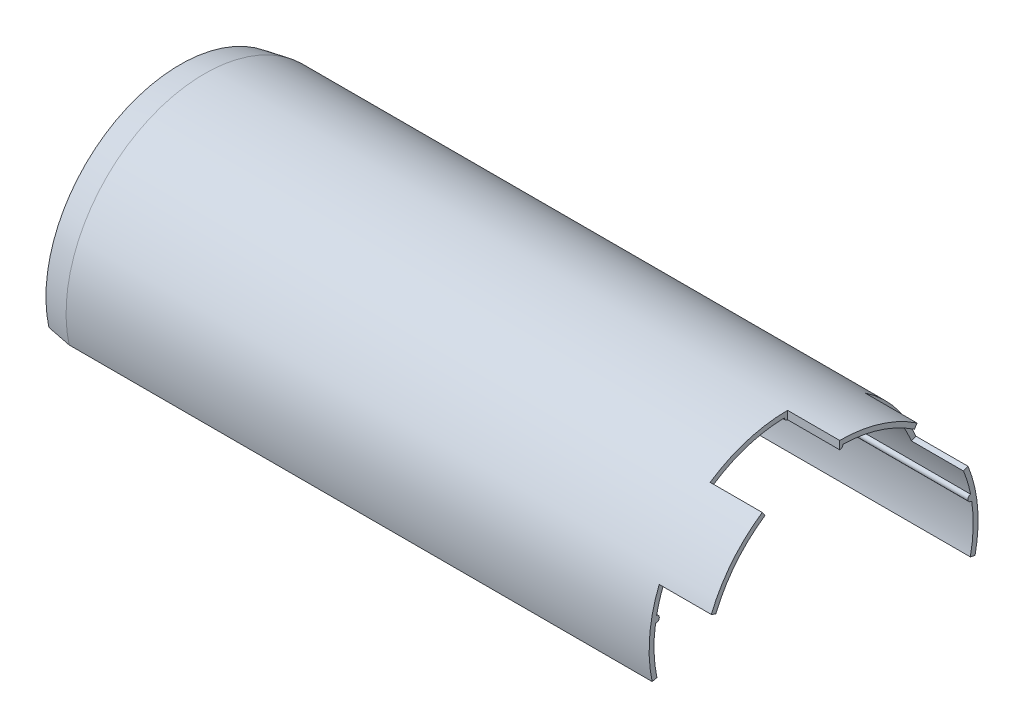
SolidWorks part; units mm, degrees
note: '?' marks a value the reader was unsure of.
material "PETG"
ref_plane "Front Plane" through (0, 0, 0) normal (0, 0, 1) x (1, 0, 0)
ref_plane "Top Plane" through (0, 0, 0) normal (0, 1, 0) x (1, 0, 0)
ref_plane "Right Plane" through (0, 0, 0) normal (1, 0, 0) x (0, 0, -1)
curve "Curve1"
  spline degree 3 poles (0, 0, 0) (-0.0123, 3.8916, 0) (-0.0274, 8.685, 0) (0.3616, 14.0857, 0) (0.5761, 16.0905, 0) (0.7825, 17.6048, 0) (0.9862, 18.8543, 0) (1.1887, 19.9315, 0) (1.3904, 20.8857, 0) (1.5917, 21.7465, 0) (1.7927, 22.5337, 0) (1.9935, 23.2611, 0) (2.1942, 23.9386, 0) (2.3947, 24.5739, 0) (2.5952, 25.1728, 0) (2.7956, 25.7401, 0) (2.9959, 26.2796, 0) (3.1962, 26.7943, 0) (3.3965, 27.2868, 0) (3.5967, 27.7594, 0) (3.7969, 28.2139, 0) (3.9971, 28.6519, 0) (4.1973, 29.0748, 0) (4.3974, 29.4838, 0) (4.5976, 29.8799, 0) (4.7977, 30.2641, 0) (4.9978, 30.6373, 0) (5.1979, 31.0001, 0) (5.398, 31.3533, 0) (5.5981, 31.6974, 0) (5.7982, 32.033, 0) (5.9983, 32.3606, 0) (6.1984, 32.6807, 0) (6.3985, 32.9935, 0) (6.5985, 33.2996, 0) (6.7986, 33.5993, 0) (6.9986, 33.8929, 0) (7.1987, 34.1806, 0) (7.3987, 34.4628, 0) (7.5988, 34.7397, 0) (7.7988, 35.0115, 0) (7.9989, 35.2785, 0) (8.1989, 35.5408, 0) (8.399, 35.7988, 0) (8.599, 36.0524, 0) (8.799, 36.3019, 0) (8.9991, 36.5476, 0) (9.1991, 36.7894, 0) (9.3991, 37.0275, 0) (9.5992, 37.2622, 0) (9.7992, 37.4934, 0) (9.9992, 37.7214, 0) (10.1992, 37.9461, 0) (10.3993, 38.1679, 0) (10.5993, 38.3866, 0) (10.7993, 38.6025, 0) (10.9993, 38.8156, 0) (11.1993, 39.026, 0) (11.3994, 39.2338, 0) (11.5994, 39.4391, 0) (11.7994, 39.6419, 0) (11.9994, 39.8422, 0) (12.1994, 40.0403, 0) (12.3995, 40.2361, 0) (12.5995, 40.4297, 0) (12.7995, 40.6212, 0) (12.9995, 40.8106, 0) (13.1995, 40.998, 0) (13.3995, 41.1834, 0) (13.5995, 41.3668, 0) (13.7995, 41.5484, 0) (13.9996, 41.7281, 0) (14.1996, 41.9061, 0) (14.3996, 42.0823, 0) (14.5996, 42.2568, 0) (14.7996, 42.4296, 0) (14.9996, 42.6008, 0) (15.1996, 42.7705, 0) (15.3996, 42.9385, 0) (15.5996, 43.1051, 0) (15.7996, 43.2701, 0) (15.9997, 43.4337, 0) (16.1997, 43.5959, 0) (16.3997, 43.7567, 0) (16.5997, 43.9161, 0) (16.7997, 44.0742, 0) (16.9997, 44.2309, 0) (17.1997, 44.3864, 0) (17.3997, 44.5406, 0) (17.5997, 44.6936, 0) (17.7997, 44.8453, 0) (17.9997, 44.9959, 0) (18.1997, 45.1453, 0) (18.3997, 45.2936, 0) (18.5997, 45.4407, 0) (18.7997, 45.5868, 0) (18.9997, 45.7317, 0) (19.1998, 45.8756, 0) (19.3998, 46.0185, 0) (19.5998, 46.1603, 0) (19.7998, 46.3011, 0) (19.9998, 46.4409, 0) (20.1998, 46.5797, 0) (20.3998, 46.7176, 0) (20.5998, 46.8546, 0) (20.7998, 46.9906, 0) (20.9998, 47.1257, 0) (21.1998, 47.2599, 0) (21.3998, 47.3932, 0) (21.5998, 47.5256, 0) (21.7998, 47.6572, 0) (21.9998, 47.788, 0) (22.1998, 47.9179, 0) (22.3998, 48.047, 0) (22.5998, 48.1753, 0) (22.7998, 48.3028, 0) (22.9998, 48.4295, 0) (23.1998, 48.5555, 0) (23.3998, 48.6807, 0) (23.5998, 48.8051, 0) (23.7998, 48.9288, 0) (23.9998, 49.0518, 0) (24.1998, 49.1741, 0) (24.3998, 49.2957, 0) (24.5998, 49.4165, 0) (24.7999, 49.5367, 0) (24.9999, 49.6562, 0) (25.1999, 49.7751, 0) (25.3999, 49.8933, 0) (25.5999, 50.0108, 0) (25.7999, 50.1277, 0) (25.9999, 50.2439, 0) (26.1999, 50.3596, 0) (26.3999, 50.4746, 0) (26.5999, 50.589, 0) (26.7999, 50.7028, 0) (26.9999, 50.8161, 0) (27.1999, 50.9287, 0) (27.3999, 51.0407, 0) (27.5999, 51.1522, 0) (27.7999, 51.2631, 0) (27.9999, 51.3735, 0) (28.1999, 51.4833, 0) (28.3999, 51.5926, 0) (28.5999, 51.7013, 0) (28.7999, 51.8095, 0) (28.9999, 51.9172, 0) (29.1999, 52.0243, 0) (29.3999, 52.131, 0) (29.5999, 52.2371, 0) (29.7999, 52.3428, 0) (29.9999, 52.4479, 0) (30.1999, 52.5526, 0) (30.3999, 52.6567, 0) (30.5999, 52.7604, 0) (30.7999, 52.8636, 0) (30.9999, 52.9664, 0) (31.1999, 53.0687, 0) (31.3999, 53.1705, 0) (31.5999, 53.2719, 0) (31.7999, 53.3728, 0) (31.9999, 53.4733, 0) (32.1999, 53.5733, 0) (32.3999, 53.6729, 0) (32.5999, 53.7721, 0) (32.7999, 53.8709, 0) (32.9999, 53.9692, 0) (33.1999, 54.0671, 0) (33.3999, 54.1646, 0) (33.5999, 54.2617, 0) (33.7999, 54.3584, 0) (33.9999, 54.4547, 0) (34.1999, 54.5506, 0) (34.3999, 54.6461, 0) (34.5999, 54.7412, 0) (34.7999, 54.836, 0) (34.9999, 54.9303, 0) (35.1999, 55.0243, 0) (35.3999, 55.1179, 0) (35.5999, 55.2111, 0) (35.7999, 55.304, 0) (35.9999, 55.3965, 0) (36.1999, 55.4887, 0) (36.3999, 55.5805, 0) (36.5999, 55.6719, 0) (36.7999, 55.763, 0) (36.9999, 55.8537, 0) (37.1999, 55.9441, 0) (37.3999, 56.0342, 0) (37.5999, 56.1239, 0) (37.7999, 56.2133, 0) (37.9999, 56.3024, 0) (38.1999, 56.3911, 0) (38.3999, 56.4795, 0) (38.5999, 56.5676, 0) (38.7999, 56.6554, 0) (38.9999, 56.7428, 0) (39.1999, 56.83, 0) (39.3999, 56.9168, 0) (39.5999, 57.0033, 0) (39.7999, 57.0896, 0) (39.9999, 57.1755, 0) (40.1999, 57.2611, 0) (40.3999, 57.3464, 0) (40.5999, 57.4314, 0) (40.7999, 57.5161, 0) (40.9999, 57.6006, 0) (41.1999, 57.6847, 0) (41.3999, 57.7686, 0) (41.6, 57.8522, 0) (41.8, 57.9355, 0) (42, 58.0185, 0) (42.2, 58.1012, 0) (42.4, 58.1837, 0) (42.6, 58.2659, 0) (42.8, 58.3479, 0) (43, 58.4295, 0) (43.2, 58.5109, 0) (43.4, 58.592, 0) (43.6, 58.6729, 0) (43.8, 58.7535, 0) (44, 58.8339, 0) (44.2, 58.914, 0) (44.4, 58.9938, 0) (44.6, 59.0734, 0) (44.8, 59.1528, 0) (45, 59.2319, 0) (45.2, 59.3107, 0) (45.4, 59.3893, 0) (45.6, 59.4677, 0) (45.8, 59.5458, 0) (46, 59.6237, 0) (46.2, 59.7014, 0) (46.4, 59.7788, 0) (46.6, 59.856, 0) (46.8, 59.9329, 0) (47, 60.0096, 0) (47.2, 60.0861, 0) (47.4, 60.1624, 0) (47.6, 60.2385, 0) (47.8, 60.3143, 0) (48, 60.3899, 0) (48.2, 60.4652, 0) (48.4, 60.5404, 0) (48.6, 60.6153, 0) (48.8, 60.6901, 0) (49, 60.7646, 0) (49.2, 60.8389, 0) (49.4, 60.913, 0) (49.6, 60.9869, 0) (49.8, 61.0605, 0) (50, 61.134, 0) (50.2, 61.2072, 0) (50.4, 61.2803, 0) (50.6, 61.3531, 0) (50.8, 61.4258, 0) (51, 61.4982, 0) (51.2, 61.5705, 0) (51.4, 61.6426, 0) (51.6, 61.7144, 0) (51.8, 61.7861, 0) (52, 61.8575, 0) (52.2, 61.9288, 0) (52.4, 61.9999, 0) (52.6, 62.0708, 0) (52.8, 62.1415, 0) (53, 62.212, 0) (53.2, 62.2824, 0) (53.4, 62.3525, 0) (53.6, 62.4225, 0) (53.8, 62.4923, 0) (54, 62.5619, 0) (54.2, 62.6313, 0) (54.4, 62.7006, 0) (54.6, 62.7696, 0) (54.8, 62.8385, 0) (55, 62.9072, 0) (55.2, 62.9758, 0) (55.4, 63.0441, 0) (55.6, 63.1123, 0) (55.8, 63.1803, 0) (56, 63.2482, 0) (56.2, 63.3159, 0) (56.4, 63.3834, 0) (56.6, 63.4507, 0) (56.8, 63.5179, 0) (57, 63.5849, 0) (57.2, 63.6518, 0) (57.4, 63.7185, 0) (57.6, 63.785, 0) (57.8, 63.8513, 0) (58, 63.9175, 0) (58.2, 63.9836, 0) (58.4, 64.0495, 0) (58.6, 64.1152, 0) (58.8, 64.1808, 0) (59, 64.2462, 0) (59.2, 64.3114, 0) (59.4, 64.3765, 0) (59.6, 64.4415, 0) (59.8, 64.5063, 0) (60, 64.5709, 0) (60.2, 64.6354, 0) (60.4, 64.6998, 0) (60.6, 64.764, 0) (60.8, 64.828, 0) (61, 64.8919, 0) (61.2, 64.9557, 0) (61.4, 65.0193, 0) (61.6, 65.0827, 0) (61.8, 65.1461, 0) (62, 65.2092, 0) (62.2, 65.2723, 0) (62.4, 65.3352, 0) (62.6, 65.3979, 0) (62.8, 65.4605, 0) (63, 65.523, 0) (63.2, 65.5853, 0) (63.4, 65.6475, 0) (63.6, 65.7096, 0) (63.8, 65.7715, 0) (64, 65.8333, 0) (64.2, 65.895, 0) (64.4, 65.9565, 0) (64.6, 66.0179, 0) (64.8, 66.0791, 0) (65, 66.1402, 0) (65.2, 66.2012, 0) (65.4, 66.2621, 0) (65.6, 66.3228, 0) (65.8, 66.3834, 0) (66, 66.4439, 0) (66.2, 66.5042, 0) (66.4, 66.5644, 0) (66.6, 66.6245, 0) (66.8, 66.6845, 0) (67, 66.7443, 0) (67.2, 66.804, 0) (67.4, 66.8636, 0) (67.6, 66.923, 0) (67.8, 66.9824, 0) (68, 67.0416, 0) (68.2, 67.1007, 0) (68.4, 67.1597, 0) (68.6, 67.2185, 0) (68.8, 67.2772, 0) (69, 67.3359, 0) (69.2, 67.3943, 0) (69.4, 67.4527, 0) (69.6, 67.511, 0) (69.8, 67.5691, 0) (70, 67.6271, 0) (70.2, 67.6851, 0) (70.4, 67.7428, 0) (70.6, 67.8005, 0) (70.8, 67.8581, 0) (71, 67.9155, 0) (71.2, 67.9729, 0) (71.4, 68.0301, 0) (71.6, 68.0872, 0) (71.8, 68.1442, 0) (72, 68.2011, 0) (72.2, 68.2579, 0) (72.4, 68.3145, 0) (72.6, 68.3711, 0) (72.8, 68.4276, 0) (73, 68.4839, 0) (73.2, 68.5401, 0) (73.4, 68.5963, 0) (73.6, 68.6523, 0) (73.8, 68.7082, 0) (74, 68.764, 0) (74.2, 68.8197, 0) (74.4, 68.8753, 0) (74.6, 68.9308, 0) (74.8, 68.9862, 0) (75, 69.0415, 0) (75.2, 69.0966, 0) (75.4, 69.1517, 0) (75.6, 69.2067, 0) (75.8, 69.2616, 0) (76, 69.3164, 0) (76.2, 69.371, 0) (76.4, 69.4256, 0) (76.6, 69.4801, 0) (76.8, 69.5344, 0) (77, 69.5887, 0) (77.2, 69.6429, 0) (77.4, 69.697, 0) (77.6, 69.751, 0) (77.8, 69.8048, 0) (78, 69.8586, 0) (78.2, 69.9123, 0) (78.4, 69.9659, 0) (78.6, 70.0194, 0) (78.8, 70.0728, 0) (79, 70.1261, 0) (79.2, 70.1793, 0) (79.4, 70.2324, 0) (79.6, 70.2855, 0) (79.8, 70.3384, 0) (80, 70.3912, 0) (80.2, 70.444, 0) (80.4, 70.4966, 0) (80.6, 70.5492, 0) (80.8, 70.6017, 0) (81, 70.6541, 0) (81.2, 70.7064, 0) (81.4, 70.7586, 0) (81.6, 70.8107, 0) (81.8, 70.8627, 0) (82, 70.9146, 0) (82.2, 70.9665, 0) (82.4, 71.0182, 0) (82.6, 71.0699, 0) (82.8, 71.1215, 0) (83, 71.173, 0) (83.2, 71.2244, 0) (83.4, 71.2757, 0) (83.6, 71.3269, 0) (83.8, 71.3781, 0) (84, 71.4291, 0) (84.2, 71.4801, 0) (84.4, 71.531, 0) (84.6, 71.5818, 0) (84.8, 71.6325, 0) (85, 71.6832, 0) (85.2, 71.7337, 0) (85.4, 71.7842, 0) (85.6, 71.8346, 0) (85.8, 71.8849, 0) (86, 71.9351, 0) (86.2, 71.9853, 0) (86.4, 72.0354, 0) (86.6, 72.0853, 0) (86.8, 72.1352, 0) (87, 72.1851, 0) (87.2, 72.2348, 0) (87.4, 72.2845, 0) (87.6, 72.3341, 0) (87.8, 72.3836, 0) (88, 72.433, 0) (88.2, 72.4823, 0) (88.4, 72.5316, 0) (88.6, 72.5808, 0) (88.8, 72.6299, 0) (89, 72.6789, 0) (89.2, 72.7279, 0) (89.4, 72.7768, 0) (89.6, 72.8256, 0) (89.8, 72.8743, 0) (90, 72.923, 0) (90.2, 72.9716, 0) (90.4, 73.0201, 0) (90.6, 73.0685, 0) (90.8, 73.1168, 0) (91, 73.1651, 0) (91.2, 73.2133, 0) (91.4, 73.2614, 0) (91.6, 73.3095, 0) (91.8, 73.3575, 0) (92, 73.4054, 0) (92.2, 73.4532, 0) (92.4, 73.501, 0) (92.6, 73.5487, 0) (92.8, 73.5963, 0) (93, 73.6439, 0) (93.2, 73.6913, 0) (93.4, 73.7387, 0) (93.6, 73.7861, 0) (93.8, 73.8333, 0) (94, 73.8805, 0) (94.2, 73.9276, 0) (94.4, 73.9747, 0) (94.6, 74.0217, 0) (94.8, 74.0686, 0) (95, 74.1154, 0) (95.2, 74.1622, 0) (95.4, 74.2089, 0) (95.6, 74.2556, 0) (95.8, 74.3021, 0) (96, 74.3486, 0) (96.2, 74.3951, 0) (96.4, 74.4414, 0) (96.6, 74.4877, 0) (96.8, 74.534, 0) (97, 74.5801, 0) (97.2, 74.6262, 0) (97.4, 74.6723, 0) (97.6, 74.7182, 0) (97.8, 74.7641, 0) (98, 74.81, 0) (98.2, 74.8557, 0) (98.4, 74.9014, 0) (98.6, 74.9471, 0) (98.8, 74.9926, 0) (99, 75.0382, 0) (99.2, 75.0836, 0) (99.4, 75.129, 0) (99.6, 75.1743, 0) (99.8, 75.2196, 0) (100, 75.2647, 0) (100.2, 75.3099, 0) (100.4, 75.3549, 0) (100.6, 75.3999, 0) (100.8, 75.4449, 0) (101, 75.4898, 0) (101.2, 75.5346, 0) (101.4, 75.5793, 0) (101.6, 75.624, 0) (101.8, 75.6686, 0) (102, 75.7132, 0) (102.2, 75.7577, 0) (102.4, 75.8022, 0) (102.6, 75.8465, 0) (102.8, 75.8909, 0) (103, 75.9351, 0) (103.2, 75.9793, 0) (103.4, 76.0235, 0) (103.6, 76.0676, 0) (103.8, 76.1116, 0) (104, 76.1556, 0) (104.2, 76.1995, 0) (104.4, 76.2433, 0) (104.6, 76.2871, 0) (104.8, 76.3308, 0) (105, 76.3745, 0) (105.2, 76.4181, 0) (105.4, 76.4617, 0) (105.6, 76.5052, 0) (105.8, 76.5486, 0) (106, 76.592, 0) (106.2, 76.6353, 0) (106.4, 76.6786, 0) (106.6, 76.7218, 0) (106.8, 76.7649, 0) (107, 76.808, 0) (107.2, 76.8511, 0) (107.4, 76.8941, 0) (107.6, 76.937, 0) (107.8, 76.9799, 0) (108, 77.0227, 0) (108.2, 77.0655, 0) (108.4, 77.1082, 0) (108.6, 77.1508, 0) (108.8, 77.1934, 0) (109, 77.236, 0) (109.2, 77.2784, 0) (109.4, 77.3209, 0) (109.6, 77.3633, 0) (109.8, 77.4056, 0) (110, 77.4479, 0) (110.2, 77.4901, 0) (110.4, 77.5322, 0) (110.6, 77.5743, 0) (110.8, 77.6164, 0) (111, 77.6584, 0) (111.2, 77.7004, 0) (111.4, 77.7423, 0) (111.6, 77.7841, 0) (111.8, 77.8259, 0) (112, 77.8676, 0) (112.2, 77.9093, 0) (112.4, 77.951, 0) (112.6, 77.9925, 0) (112.8, 78.0341, 0) (113, 78.0756, 0) (113.2, 78.117, 0) (113.4, 78.1584, 0) (113.6, 78.1997, 0) (113.8, 78.241, 0) (114, 78.2822, 0) (114.2, 78.3234, 0) (114.4, 78.3645, 0) (114.6, 78.4056, 0) (114.8, 78.4466, 0) (115, 78.4876, 0) (115.2, 78.5285, 0) (115.4, 78.5694, 0) (115.6, 78.6102, 0) (115.8, 78.651, 0) (116, 78.6917, 0) (116.2, 78.7324, 0) (116.4, 78.773, 0) (116.6, 78.8136, 0) (116.8, 78.8541, 0) (117, 78.8946, 0) (117.2, 78.935, 0) (117.4, 78.9754, 0) (117.6, 79.0158, 0) (117.8, 79.0561, 0) (118, 79.0963, 0) (118.2, 79.1365, 0) (118.4, 79.1766, 0) (118.6, 79.2167, 0) (118.8, 79.2568, 0) (119, 79.2968, 0) (119.2, 79.3368, 0) (119.4, 79.3767, 0) (119.6, 79.4165, 0) (119.8, 79.4564, 0) (120, 79.4961, 0) (120.2, 79.5358, 0) (120.4, 79.5755, 0) (120.6, 79.6152, 0) (120.8, 79.6547, 0) (121, 79.6943, 0) (121.2, 79.7338, 0) (121.4, 79.7732, 0) (121.6, 79.8126, 0) (121.8, 79.852, 0) (122, 79.8913, 0) (122.2, 79.9306, 0) (122.4, 79.9698, 0) (122.6, 80.009, 0) (122.8, 80.0481, 0) (123, 80.0872, 0) (123.2, 80.1262, 0) (123.4, 80.1652, 0) (123.6, 80.2042, 0) (123.8, 80.2431, 0) (124, 80.282, 0) (124.2, 80.3208, 0) (124.4, 80.3596, 0) (124.6, 80.3983, 0) (124.8, 80.437, 0) (125, 80.4757, 0) (125.2, 80.5143, 0) (125.4, 80.5528, 0) (125.6, 80.5914, 0) (125.8, 80.6298, 0) (126, 80.6683, 0) (126.2, 80.7067, 0) (126.4, 80.745, 0) (126.6, 80.7833, 0) (126.8, 80.8216, 0) (127, 80.8598, 0) (127.2, 80.898, 0) (127.4, 80.9361, 0) (127.6, 80.9742, 0) (127.8, 81.0123, 0) (128, 81.0503, 0) (128.2, 81.0883, 0) (128.4, 81.1262, 0) (128.6, 81.1641, 0) (128.8, 81.2019, 0) (129, 81.2397, 0) (129.2, 81.2775, 0) (129.4, 81.3152, 0) (129.6, 81.3529, 0) (129.8, 81.3906, 0) (130, 81.4282, 0) (130.2, 81.4657, 0) (130.4, 81.5032, 0) (130.6, 81.5407, 0) (130.8, 81.5782, 0) (131, 81.6156, 0) (131.2, 81.6529, 0) (131.4, 81.6902, 0) (131.6, 81.7275, 0) (131.8, 81.7648, 0) (132, 81.802, 0) (132.2, 81.8391, 0) (132.4, 81.8763, 0) (132.6, 81.9133, 0) (132.8, 81.9504, 0) (133, 81.9874, 0) (133.2, 82.0244, 0) (133.4, 82.0613, 0) (133.6, 82.0982, 0) (133.8, 82.135, 0) (134, 82.1718, 0) (134.2, 82.2086, 0) (134.4, 82.2454, 0) (134.6, 82.282, 0) (134.8, 82.3187, 0) (135, 82.3553, 0) (135.2, 82.3919, 0) (135.4, 82.4285, 0) (135.6, 82.465, 0) (135.8, 82.5014, 0) (136, 82.5379, 0) (136.2, 82.5743, 0) (136.4, 82.6106, 0) (136.6, 82.6469, 0) (136.8, 82.6832, 0) (137, 82.7195, 0) (137.2, 82.7557, 0) (137.4, 82.7919, 0) (137.6, 82.828, 0) (137.8, 82.8641, 0) (138, 82.9001, 0) (138.2, 82.9362, 0) (138.4, 82.9722, 0) (138.6, 83.0081, 0) (138.8, 83.044, 0) (139, 83.0799, 0) (139.2, 83.1158, 0) (139.4, 83.1516, 0) (139.6, 83.1873, 0) (139.8, 83.2231, 0) (140, 83.2588, 0) (140.2, 83.2944, 0) (140.4, 83.3301, 0) (140.6, 83.3657, 0) (140.8, 83.4012, 0) (141, 83.4367, 0) (141.2, 83.4722, 0) (141.4, 83.5077, 0) (141.6, 83.5431, 0) (141.8, 83.5785, 0) (142, 83.6138, 0) (142.2, 83.6491, 0) (142.4, 83.6844, 0) (142.6, 83.7197, 0) (142.8, 83.7549, 0) (143, 83.79, 0) (143.2, 83.8252, 0) (143.4, 83.8603, 0) (143.6, 83.8954, 0) (143.8, 83.9304, 0) (144, 83.9654, 0) (144.2, 84.0004, 0) (144.4, 84.0353, 0) (144.6, 84.0702, 0) (144.8, 84.1051, 0) (145, 84.1399, 0) (145.2, 84.1747, 0) (145.4, 84.2095, 0) (145.6, 84.2442, 0) (145.8, 84.2789, 0) (146, 84.3136, 0) (146.2, 84.3482, 0) (146.4, 84.3828, 0) (146.6, 84.4174, 0) (146.8, 84.4519, 0) (147, 84.4864, 0) (147.2, 84.5209, 0) (147.4, 84.5553, 0) (147.6, 84.5897, 0) (147.8, 84.6241, 0) (148, 84.6584, 0) (148.2, 84.6927, 0) (148.4, 84.727, 0) (148.6, 84.7612, 0) (148.8, 84.7954, 0) (149, 84.8296, 0) (149.2, 84.8638, 0) (149.4, 84.8979, 0) (149.6, 84.9319, 0) (149.8, 84.966, 0) (149.9333, 84.9887, 0) (150, 85, 0) knots 0 0 0 0 0.061462 0.075706 0.085548 0.093322 0.099856 0.105554 0.110643 0.115268 0.119525 0.123482 0.127192 0.130691 0.13401 0.137173 0.140199 0.143104 0.145901 0.148602 0.151215 0.15375 0.156213 0.158609 0.160946 0.163227 0.165456 0.167638 0.169775 0.171871 0.173928 0.17595 0.177937 0.179893 0.181819 0.183716 0.185587 0.187433 0.189255 0.191054 0.192831 0.194589 0.196326 0.198045 0.199747 0.201431 0.2031 0.204753 0.206391 0.208015 0.209626 0.211223 0.212808 0.214381 0.215942 0.217493 0.219032 0.220561 0.22208 0.22359 0.225091 0.226582 0.228065 0.229539 0.231006 0.232464 0.233915 0.235359 0.236795 0.238225 0.239648 0.241065 0.242475 0.243879 0.245277 0.24667 0.248057 0.249438 0.250814 0.252185 0.253551 0.254913 0.256269 0.257621 0.258968 0.260311 0.26165 0.262984 0.264315 0.265641 0.266964 0.268282 0.269598 0.270909 0.272217 0.273522 0.274823 0.276121 0.277416 0.278707 0.279996 0.281281 0.282564 0.283843 0.28512 0.286394 0.287666 0.288935 0.290201 0.291465 0.292726 0.293985 0.295241 0.296495 0.297747 0.298996 0.300243 0.301489 0.302732 0.303972 0.305211 0.306448 0.307683 0.308916 0.310147 0.311376 0.312604 0.313829 0.315053 0.316275 0.317495 0.318714 0.319931 0.321147 0.32236 0.323573 0.324783 0.325993 0.3272 0.328406 0.329611 0.330815 0.332017 0.333217 0.334416 0.335614 0.336811 0.338006 0.3392 0.340393 0.341584 0.342775 0.343964 0.345152 0.346339 0.347524 0.348709 0.349892 0.351074 0.352256 0.353436 0.354615 0.355793 0.35697 0.358146 0.359321 0.360495 0.361668 0.36284 0.364011 0.365182 0.366351 0.36752 0.368687 0.369854 0.37102 0.372185 0.373349 0.374512 0.375674 0.376836 0.377997 0.379157 0.380316 0.381475 0.382632 0.383789 0.384946 0.386101 0.387256 0.38841 0.389563 0.390716 0.391868 0.393019 0.39417 0.39532 0.396469 0.397618 0.398766 0.399913 0.40106 0.402206 0.403351 0.404496 0.40564 0.406784 0.407927 0.409069 0.410211 0.411353 0.412493 0.413633 0.414773 0.415912 0.417051 0.418189 0.419326 0.420463 0.4216 0.422736 0.423871 0.425006 0.426141 0.427275 0.428408 0.429541 0.430674 0.431806 0.432937 0.434068 0.435199 0.436329 0.437459 0.438588 0.439717 0.440846 0.441974 0.443101 0.444229 0.445355 0.446482 0.447608 0.448733 0.449858 0.450983 0.452107 0.453231 0.454355 0.455478 0.456601 0.457723 0.458845 0.459967 0.461088 0.462209 0.46333 0.46445 0.46557 0.46669 0.467809 0.468928 0.470046 0.471164 0.472282 0.4734 0.474517 0.475634 0.47675 0.477866 0.478982 0.480098 0.481213 0.482328 0.483443 0.484557 0.485671 0.486785 0.487898 0.489011 0.490124 0.491237 0.492349 0.493461 0.494573 0.495684 0.496796 0.497906 0.499017 0.500127 0.501237 0.502347 0.503457 0.504566 0.505675 0.506784 0.507892 0.509001 0.510109 0.511216 0.512324 0.513431 0.514538 0.515645 0.516752 0.517858 0.518964 0.52007 0.521175 0.522281 0.523386 0.524491 0.525595 0.5267 0.527804 0.528908 0.530012 0.531116 0.532219 0.533322 0.534425 0.535528 0.53663 0.537733 0.538835 0.539937 0.541038 0.54214 0.543241 0.544342 0.545443 0.546544 0.547644 0.548745 0.549845 0.550945 0.552044 0.553144 0.554243 0.555342 0.556441 0.55754 0.558639 0.559737 0.560836 0.561934 0.563032 0.564129 0.565227 0.566324 0.567421 0.568518 0.569615 0.570712 0.571809 0.572905 0.574001 0.575097 0.576193 0.577289 0.578384 0.57948 0.580575 0.58167 0.582765 0.58386 0.584954 0.586049 0.587143 0.588237 0.589331 0.590425 0.591519 0.592612 0.593706 0.594799 0.595892 0.596985 0.598078 0.59917 0.600263 0.601355 0.602448 0.60354 0.604632 0.605724 0.606815 0.607907 0.608998 0.61009 0.611181 0.612272 0.613363 0.614453 0.615544 0.616635 0.617725 0.618815 0.619905 0.620995 0.622085 0.623175 0.624265 0.625354 0.626443 0.627533 0.628622 0.629711 0.6308 0.631888 0.632977 0.634066 0.635154 0.636242 0.637331 0.638419 0.639507 0.640594 0.641682 0.64277 0.643857 0.644945 0.646032 0.647119 0.648206 0.649293 0.65038 0.651467 0.652553 0.65364 0.654726 0.655813 0.656899 0.657985 0.659071 0.660157 0.661243 0.662328 0.663414 0.664499 0.665585 0.66667 0.667755 0.66884 0.669925 0.67101 0.672095 0.67318 0.674264 0.675349 0.676433 0.677518 0.678602 0.679686 0.68077 0.681854 0.682938 0.684022 0.685105 0.686189 0.687272 0.688356 0.689439 0.690522 0.691605 0.692688 0.693771 0.694854 0.695937 0.69702 0.698102 0.699185 0.700267 0.70135 0.702432 0.703514 0.704596 0.705678 0.70676 0.707842 0.708924 0.710006 0.711087 0.712169 0.71325 0.714332 0.715413 0.716494 0.717575 0.718656 0.719737 0.720818 0.721899 0.72298 0.724061 0.725141 0.726222 0.727302 0.728382 0.729463 0.730543 0.731623 0.732703 0.733783 0.734863 0.735943 0.737023 0.738103 0.739182 0.740262 0.741341 0.742421 0.7435 0.744579 0.745659 0.746738 0.747817 0.748896 0.749975 0.751054 0.752133 0.753211 0.75429 0.755369 0.756447 0.757526 0.758604 0.759682 0.760761 0.761839 0.762917 0.763995 0.765073 0.766151 0.767229 0.768307 0.769385 0.770462 0.77154 0.772618 0.773695 0.774773 0.77585 0.776927 0.778005 0.779082 0.780159 0.781236 0.782313 0.78339 0.784467 0.785544 0.786621 0.787698 0.788774 0.789851 0.790928 0.792004 0.793081 0.794157 0.795233 0.79631 0.797386 0.798462 0.799538 0.800614 0.80169 0.802766 0.803842 0.804918 0.805994 0.80707 0.808145 0.809221 0.810296 0.811372 0.812447 0.813523 0.814598 0.815674 0.816749 0.817824 0.818899 0.819974 0.821049 0.822124 0.823199 0.824274 0.825349 0.826424 0.827499 0.828573 0.829648 0.830723 0.831797 0.832872 0.833946 0.835021 0.836095 0.837169 0.838244 0.839318 0.840392 0.841466 0.84254 0.843614 0.844688 0.845762 0.846836 0.84791 0.848984 0.850058 0.851131 0.852205 0.853279 0.854352 0.855426 0.856499 0.857573 0.858646 0.859719 0.860793 0.861866 0.862939 0.864012 0.865085 0.866159 0.867232 0.868305 0.869378 0.87045 0.871523 0.872596 0.873669 0.874742 0.875814 0.876887 0.87796 0.879032 0.880105 0.881177 0.88225 0.883322 0.884395 0.885467 0.886539 0.887611 0.888684 0.889756 0.890828 0.8919 0.892972 0.894044 0.895116 0.896188 0.89726 0.898332 0.899404 0.900475 0.901547 0.902619 0.90369 0.904762 0.905834 0.906905 0.907977 0.909048 0.91012 0.911191 0.912262 0.913334 0.914405 0.915476 0.916548 0.917619 0.91869 0.919761 0.920832 0.921903 0.922974 0.924045 0.925116 0.926187 0.927258 0.928329 0.929399 0.93047 0.931541 0.932612 0.933682 0.934753 0.935823 0.936894 0.937965 0.939035 0.940105 0.941176 0.942246 0.943317 0.944387 0.945457 0.946527 0.947598 0.948668 0.949738 0.950808 0.951878 0.952948 0.954018 0.955088 0.956158 0.957228 0.958298 0.959368 0.960438 0.961508 0.962577 0.963647 0.964717 0.965786 0.966856 0.967926 0.968995 0.970065 0.971134 0.972204 0.973273 0.974343 0.975412 0.976481 0.977551 0.97862 0.979689 0.980759 0.981828 0.982897 0.983966 0.985035 0.986104 0.987173 0.988242 0.989311 0.99038 0.991449 0.992518 0.993587 0.994656 0.995725 0.996794 0.997863 0.998931 1 1 1 1
sketch "Sketch1" plane through (0, 0, 0) normal (0, 0, 1) x (1, 0, 0)
  line L0 (150, 85) -> (540, 85)
  line L1 (150.2533, 82) -> (540, 82)
  line L2 (540, 85) -> (540, 82)
  line L3 (0, 0) -> (3, 0)
  line L4 (3, 0.0095) -> (3, 0)
  line L5 (3, 0) -> (540, 0) construction
  line L6 (540, 0) -> (540, 82) construction
  line L8 (140, -75) -> (540, -75) construction
  line L9 (140, -75) -> (140, 75) construction
  line L10 (135, 79.3054) -> (135, 78.3)
  line L11 (135, 78.3) -> (129.5999, 78.3)
  line L12 (140, 75) -> (540, 75) construction
  line L13 (540, -75) -> (540, 75) construction
  line L14 (140, -75) -> (540, 75) construction
  line L15 (140, 75) -> (540, -75) construction
  spline S0 degree 3 poles (-1988.6566, -159.7184) (98.3599, -158.1291) (-5.7084, -70.1856) (0.3616, 14.0857) (0.5761, 16.0905) (0.7825, 17.6048) (0.9862, 18.8543) (1.1887, 19.9315) (1.3904, 20.8857) (1.5917, 21.7465) (1.7927, 22.5337) (1.9935, 23.2611) (2.2538, 24.14) (2.5806, 25.1462) (2.9836, 26.2595) (3.3859, 27.2713) (3.7877, 28.2016) (4.1891, 29.0648) (4.5903, 29.8717) (5.0533, 30.7478) (5.5832, 31.6835) (6.1854, 32.6697) (6.7872, 33.5906) (7.4515, 34.5461) (8.1828, 35.531) (8.9851, 36.54) (9.8503, 37.5625) (10.7826, 38.5957) (11.785, 39.6369) (12.851, 40.6804) (13.984, 41.7246) (15.1862, 42.7682) (16.388, 43.7553) (17.6544, 44.7435) (18.9876, 45.7315) (20.3892, 46.7179) (21.7905, 47.6579) (23.2571, 48.5984) (24.7904, 49.5382) (26.3916, 50.4762) (28.0583, 51.4122) (29.7917, 52.3451) (31.5927, 53.2742) (33.4594, 54.1996) (35.3929, 55.1207) (37.4597, 56.0672) (39.5933, 57.0066) (41.8602, 57.9666) (44.1937, 58.9175) (46.6606, 59.8853) (49.2604, 60.8677) (51.994, 61.8617) (54.861, 62.8656) (57.7946, 63.8556) (60.8615, 64.8536) (64.0615, 65.8584) (67.4615, 66.8882) (70.9951, 67.9202) (74.6621, 68.9539) (78.4621, 69.9886) (82.4622, 71.0404) (86.6623, 72.1071) (91.0624, 73.1864) (95.6625, 74.2764) (100.4626, 75.3753) (105.4628, 76.4816) (110.6629, 77.5938) (116.063, 78.7107) (121.6632, 79.8312) (127.5299, 80.9671) (133.6633, 82.1162) (140.0634, 83.2764) (145.1985, 84.1774) (148.3332, 84.7158) (149.3333, 84.8865) (149.6, 84.9319) (194.4783, 92.5723) (239.7917, 97.2513) (-50.3187, 2073.1568) knots -1.249314 -1.249314 -1.249314 -1.249314 0.061462 0.075706 0.085548 0.093322 0.099856 0.105554 0.110643 0.115268 0.119525 0.123482 0.127192 0.13401 0.140199 0.145901 0.151215 0.156213 0.160946 0.165456 0.171871 0.177937 0.183716 0.189255 0.196326 0.2031 0.209626 0.217493 0.225091 0.232464 0.241065 0.249438 0.257621 0.265641 0.274823 0.283843 0.292726 0.301489 0.311376 0.321147 0.330815 0.341584 0.352256 0.36284 0.374512 0.386101 0.398766 0.411353 0.425006 0.438588 0.453231 0.468928 0.484557 0.501237 0.517858 0.535528 0.554243 0.574001 0.593706 0.614453 0.636242 0.659071 0.682938 0.707842 0.733783 0.760761 0.788774 0.817824 0.84791 0.879032 0.912262 0.946527 0.981828 0.994656 0.996794 0.997863 0.998931 1.716252 1.716252 1.716252 1.716252 only from (0, 0) to (150, 85) construction
  spline S1 degree 3 poles (0, 0) (-0.0123, 3.8916) (-0.0274, 8.685) (0.3616, 14.0857) (0.5761, 16.0905) (0.7825, 17.6048) (0.9862, 18.8543) (1.1887, 19.9315) (1.3904, 20.8857) (1.5917, 21.7465) (1.7927, 22.5337) (1.9935, 23.2611) (2.2538, 24.14) (2.5806, 25.1462) (2.9836, 26.2595) (3.3859, 27.2713) (3.7877, 28.2016) (4.1891, 29.0648) (4.5903, 29.8717) (5.0533, 30.7478) (5.5832, 31.6835) (6.1854, 32.6697) (6.7872, 33.5906) (7.4515, 34.5461) (8.1828, 35.531) (8.9851, 36.54) (9.8503, 37.5625) (10.7826, 38.5957) (11.785, 39.6369) (12.851, 40.6804) (13.984, 41.7246) (15.1862, 42.7682) (16.388, 43.7553) (17.6544, 44.7435) (18.9876, 45.7315) (20.3892, 46.7179) (21.7905, 47.6579) (23.2571, 48.5984) (24.7904, 49.5382) (26.3916, 50.4762) (28.0583, 51.4122) (29.7917, 52.3451) (31.5927, 53.2742) (33.4594, 54.1996) (35.3929, 55.1207) (37.4597, 56.0672) (39.5933, 57.0066) (41.8602, 57.9666) (44.1937, 58.9175) (46.6606, 59.8853) (49.2604, 60.8677) (51.994, 61.8617) (54.861, 62.8656) (57.7946, 63.8556) (60.8615, 64.8536) (64.0615, 65.8584) (67.4615, 66.8882) (70.9951, 67.9202) (74.6621, 68.9539) (78.4621, 69.9886) (82.4622, 71.0404) (86.6623, 72.1071) (91.0624, 73.1864) (95.6625, 74.2764) (100.4626, 75.3753) (105.4628, 76.4816) (110.6629, 77.5938) (116.063, 78.7107) (121.6632, 79.8312) (127.5299, 80.9671) (133.6633, 82.1162) (140.0634, 83.2764) (145.1985, 84.1774) (148.3332, 84.7158) (149.4, 84.8979) (149.7333, 84.9547) (149.9333, 84.9887) (150, 85) knots 0 0 0 0 0.061462 0.075706 0.085548 0.093322 0.099856 0.105554 0.110643 0.115268 0.119525 0.123482 0.127192 0.13401 0.140199 0.145901 0.151215 0.156213 0.160946 0.165456 0.171871 0.177937 0.183716 0.189255 0.196326 0.2031 0.209626 0.217493 0.225091 0.232464 0.241065 0.249438 0.257621 0.265641 0.274823 0.283843 0.292726 0.301489 0.311376 0.321147 0.330815 0.341584 0.352256 0.36284 0.374512 0.386101 0.398766 0.411353 0.425006 0.438588 0.453231 0.468928 0.484557 0.501237 0.517858 0.535528 0.554243 0.574001 0.593706 0.614453 0.636242 0.659071 0.682938 0.707842 0.733783 0.760761 0.788774 0.817824 0.84791 0.879032 0.912262 0.946527 0.981828 0.994656 0.996794 0.998931 1 1 1 1
  spline S4 degree 1 poles (3, 0.0095) (150.2533, 82) knots 0 0 1 1 construction
  spline S5 degree 3 poles (3, 0.0095) (2.9938, 1.9694) (2.982, 5.9112) (3.1447, 11.6915) (3.6709, 17.3262) (4.8192, 22.7297) (6.752, 27.816) (10.434, 34.0689) (16.886, 40.7698) (26.3115, 47.2193) (36.5885, 52.5329) (47.3393, 57.0416) (62.0527, 62.2707) (80.8898, 67.7174) (103.8027, 73.1709) (119.6464, 76.4013) (128.7004, 78.1304) (130.4993, 78.4702) (132.2991, 78.8064) (134.0994, 79.1404) (140.0771, 80.2374) (145.6154, 81.2107) (150.2533, 82) knots 0 0 0 0 0.031208 0.062417 0.093625 0.124833 0.156041 0.18725 0.249666 0.312083 0.374499 0.436916 0.499332 0.624165 0.748998 0.873334 0.880588 0.895097 0.902352 0.909606 0.924115 0.998664 0.998664 0.998664 0.998664
  point P3 (340, 0)
  dimension "D7" = 156.6
  dimension "D1" = 400
  dimension "D4" = 150
  dimension "D6" = 5
  dimension "D2" = 0
  dimension "D3" = 3
revolve "Revolve5" add sketch "Sketch1" angle 360 about L5
sketch "Sketch12" plane through (540, 0, 0) normal (1, 0, 0) x (0, 0, -1)
  line L0 (0, 0) -> (-83.1425, -17.6725)
  line L1 (0, 55) -> (0, -55) construction
  line L2 (0, 0) -> (83.1425, -17.6725)
  circle A0 centre (0, 0) radius 85 construction
  arc A1 (-83.1425, -17.6725) -> (83.1425, -17.6725) centre (0, 0) ccw
  dimension "D1" = 204
extrude "Cut-Extrude4" cut sketch "Sketch12" against normal up to surface (405 mm away) up to face at (135, 0, 78.3)
ref_axis "Axis1" through (150, -17.6725, 83.1425) along (1, 0, 0)?
sketch "Sketch4" plane through (135, 0, 0) normal (1, 0, 0) x (0, 0, -1)
  line L10 (83.1425, -17.6725) -> (80.5557, -17.1226)
  line L13 (83.1425, -17.6725) -> (0, 0) construction
  line L14 (-80.5557, -17.1226) -> (-83.1425, -17.6725)
  line L15 (-80.5557, -17.1226) -> (-83.1425, -17.6725)
  line L16 (0, 0) -> (69.8413, -43.6417) construction
  line L17 (77.5723, -16.4885) -> (80.5557, -17.1226) construction
  line L19 (58.6889, -12.4747) -> (80.5557, -17.1226)
  arc A16 (83.1425, -17.6725) -> (-83.1425, -17.6725) centre (0, 0) ccw
  arc A18 (-80.5557, -17.1226) -> (80.5557, -17.1226) centre (0, 0) ccw
  arc A23 (40.2576, -71.8452) -> (50.8829, -31.7952) centre (-83.1425, -17.6725) ccw
  arc A24 (50.8829, -31.7952) -> (58.6889, -12.4747) centre (0, 0) ccw
  arc A26 (-80.5557, -17.1226) -> (80.5557, -17.1226) centre (0, 0) ccw construction
  arc A28 (40.2576, -71.8452) -> (80.5557, -17.1226) centre (0, 0) ccw
  dimension "D2" = 120
  dimension "D1" = 20
extrude "Cut-Extrude1" cut sketch "Sketch4" against normal blind 5
sketch "Sketch5" plane through (0, 0, 0) normal (0, 0, 1) x (1, 0, 0)
  line L1 (55, 0) -> (-55, 0) construction
  line L3 (135, 0) -> (129.5999, 0) construction
  line L4 (135, -82.3553) -> (135, -17.1226) construction
  circle A1 centre (132.5, 0) radius 1.025
  dimension "D1" = 2.05
  dimension "D2" = 2.5
sketch "Sketch10" plane through (540, 0, 0) normal (1, 0, 0) x (0, 0, -1)
  circle A0 centre (0, 82) radius 2
  arc A2 (80.2081, -17.0488) -> (-80.2081, -17.0488) centre (0, 0) ccw construction
  dimension "D1" = 4
extrude "Boss-Extrude1" add sketch "Sketch10" against normal up to next
pattern_circular "CirPattern1" count 2 every 80 about axis through (3, 0, 0) along (-1, 0, 0) of "Boss-Extrude1"
hole_wizard "Ø2.0mm Dowel Hole1" positions "3DSketch3" profile "Sketch16" hole size "Ø2.0" standard "ISO" end condition up to next
sketch3d "3DSketch3"
  line L7 (540, 0, 0) -> (150.2533, 0, 0) construction
  line L8 (181.1187, 0, 0) -> (65.6425, 0, 0) construction
  circle A3 centre (132.5, 0, 0) radius 78.3 construction
  arc A4 (135, -65.5435, -42.8361) -> (135, -16.2795, -76.589) centre (135, 0, 0) ccw construction
  point P89 (210.8, 0, 0)
  point P99 (56.7, 0, 0)
  point P103 (132.5, 0, 78.3)
  point P105 (132.5, 78.3, 0)
  point P107 (132.5, 0, -78.3)
  point P109 (132.5, -78.3, 0)
  dimension "D1" = 2.5
sketch "Sketch16" plane through (132.5, -78.3, 0) normal (1, 0, 0) x (0, 0, 1)
  line L0 (0, 0) -> (0, 3.5948)
  line L1 (0, 3.5948) -> (1, 3.5948)
  line L2 (1, 3.5948) -> (1, 0)
  line L5 (1, 0) -> (0, 0)
  line L11 (0, -6.35) -> (0, 107.95) construction
  dimension "Thru Hole Dia." = 2
  dimension "Thru Hole Depth" = 3.5948
sketch "Sketch18" plane through (540, 0, 0) normal (1, 0, 0) x (0, 0, -1)
  line L0 (-80.2081, -17.0488) -> (-83.1425, -17.6725)
  line L1 (-76.0291, 30.7177) -> (-78.8106, 31.8416)
  line L2 (0, 0) -> (-80.2081, -17.0488) construction
  line L3 (0, 0) -> (-76.0291, 30.7177) construction
  line L4 (-76.0291, 30.7177) -> (0, 0)
  line L5 (0, 0) -> (-80.2081, -17.0488)
  arc A0 (83.1425, -17.6725) -> (-83.1425, -17.6725) centre (0, 0) ccw construction
  arc A1 (-1.9999, 81.9756) -> (-80.3829, 16.2044) centre (0, 0) ccw construction
  arc A2 (-81.0775, 12.2654) -> (-80.3829, 16.2044) centre (-80.7542, 14.2392) ccw construction
  arc A3 (-81.0775, 12.2654) -> (-80.2081, -17.0488) centre (0, 0) ccw construction
  arc A4 (-78.8106, 31.8416) -> (-83.1425, -17.6725) centre (0, 0) ccw
  arc A5 (-76.0291, 30.7177) -> (-80.3829, 16.2044) centre (0, 0) ccw construction
  arc A6 (-81.0775, 12.2654) -> (-80.3829, 16.2044) centre (-80.7542, 14.2392) ccw construction
  arc A7 (-81.0775, 12.2654) -> (-80.2081, -17.0488) centre (0, 0) ccw construction
  dimension "D1" = 34
extrude "Cut-Extrude5" cut sketch "Sketch18" against normal blind 32
pattern_circular "CirPattern2" count 3 every 68 about axis through (0, 0, 0) along (1, 0, 0) of "Cut-Extrude5"
sketch "Sketch19" plane through (135, 0, 0) normal (1, 0, 0) x (0, 0, -1)
  circle A0 centre (0, 0) radius 118.9822
extrude "Cut-Extrude6" cut sketch "Sketch19" against normal blind 180
equation "\"CanSat_Len\"= 400mm"
equation "\"CanSat_Dia\"= 150mm"
equation "\"BodyTube_ID\"= 114mm"
equation "\"BodyTube_OD\"= 120mm"
equation "\"PayLoadBay_ID\"= 164mm"
equation "\"PayLoadBay_OD\"= 170mm"
equation "\"ParachuteBay_Pitch\"= 300mm"
equation "\"ElectronicsTray_PitchDist\"= 50mm"
equation "\"ElectronicsTray_Height\"= 140mm"
equation "\"MotorDia\"= 98mm"
equation "\"MotorLen\"=289mm"
equation "\"D1@Sketch1\"=\"CanSat_Len\""
equation "\"D4@Sketch1\"=\"CanSat_Dia\""
equation "\"NosePlateDia\"= 156.6mm"
equation "\"D7@Sketch1\"=\"NosePlateDia\""
